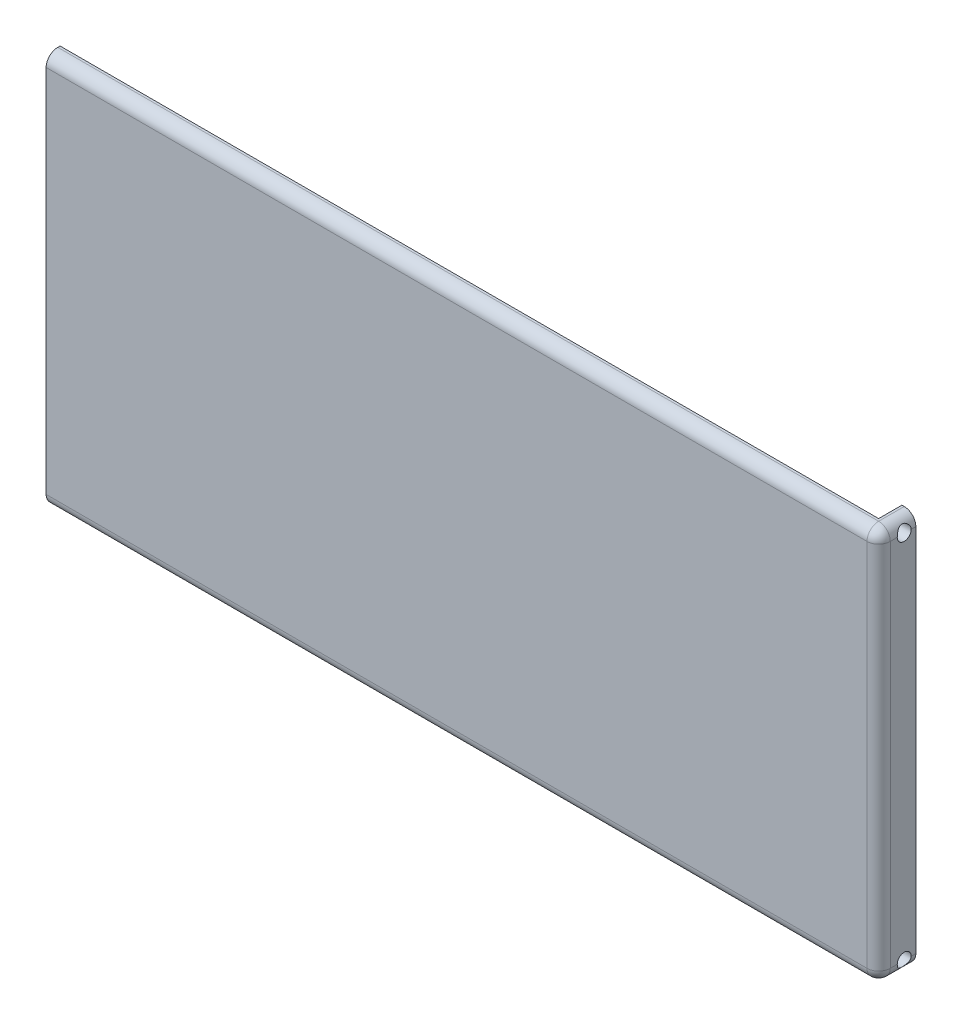
SolidWorks part; units mm, degrees
ref_plane "Front Plane" through (0, 0, 0) normal (0, 0, 1) x (1, 0, 0)
ref_plane "Top Plane" through (0, 0, 0) normal (0, 1, 0) x (1, 0, 0)
ref_plane "Right Plane" through (0, 0, 0) normal (1, 0, 0) x (0, 0, -1)
sketch "Sketch1" plane through (0, 0, 0) normal (0, 0, 1) x (1, 0, 0)
  line L1 (0, 0) -> (176, 0)
  line L2 (0, 0) -> (0, -84.5)
  line L3 (0, -84.5) -> (176, -84.5)
  line L4 (176, 0) -> (176, -84.5)
  point P4 (0, 0)
  dimension "D1" = 84.5
  dimension "D2" = 176
extrude "Boss-Extrude1" add sketch "Sketch1" along normal blind 3
sketch "Sketch2" plane through (176, 0, 0) normal (1, 0, 0) x (0, 0, -1)
  line L1 (-3, 0) -> (5, 0)
  line L2 (-3, 0) -> (-3, -5)
  line L3 (-3, -5) -> (5, -5)
  line L4 (5, 0) -> (5, -5)
  dimension "D1" = 5
  dimension "D2" = 8
extrude "Boss-Extrude2" add sketch "Sketch2" along normal blind 3
sketch "Sketch3" plane through (176, 0, 0) normal (-1, 0, 0) x (0, 0, 1)
  line L0 (0, -5) -> (0, -2.5) construction
  line L1 (0, -5) -> (0, 0) construction
  line L2 (0, -2.5) -> (-2.5, -2.5) construction
  line L3 (0, 0) -> (0, -84.5) construction
  circle A0 centre (-2.5, -2.5) radius 1.5
  dimension "D1" = 2.5
  dimension "D2" = 3
extrude "Cut-Extrude1" cut sketch "Sketch3" against normal blind 3
ref_plane "Plane4" through (0, -42.25, 0) normal (0, -1, 0) x (-1, 0, 0)
mirror "Mirror3" about plane through (0, -42.25, 0) normal (0, -1, 0) of "Cut-Extrude1", "Boss-Extrude2"
sketch "Sketch4" plane through (0, -79.5, 0) normal (0, 1, 0) x (1, 0, 0)
  line L1 (179, 5) -> (176, 5)
  line L2 (179, 5) -> (179, -3)
  line L3 (179, -3) -> (176, -3)
  line L4 (176, 5) -> (176, -3)
  point P5 (178.9287, 5)
  point P6 (0, 0)
extrude "Boss-Extrude3" add sketch "Sketch4" along normal up to surface (74.5 mm away) up to face at (177.2, -5, -0.8)
ref_plane "Plane5" through (89.5, 0, 0) normal (1, 0, 0) x (0, 0, -1)
ref_plane "Plane6" through (0, -70, 0) normal (0, -1, 0) x (-1, 0, 0)
ref_point "Point2"
sketch "Sketch12" plane through (0, -70, 0) normal (0, -1, 0) x (-1, 0, 0)
  line L0 (-176, -2.5) -> (-176, 0)
  line L1 (-176, 0) -> (-176, 5)
  line L2 (-176, 5) -> (-178.5, 5)
  line L3 (-178.5, 5) -> (-178.5, 0)
  arc A0 (-176, -2.5) -> (-178.5, 0) centre (-176, 0) cw
  dimension "D1" = 5
  dimension "D2" = 2.5
extrude "Cut-Extrude2" cut sketch "Sketch12" against normal blind 3.1
fillet "Fillet3" radius 2.5 1 edges at (179, -42.25, 3) type face fillet first side face at (179, -2.5, -1) second side face at (89.5, -42.25, 3)
fillet "Fillet4" radius 2.5 2 edges at (179, -84.5, -2.25) (88.25, -84.5, 3) type face fillet first side face at (126.7168, -84.5, -0.426) second side face at (88.25, -42.25, 3) second side face at (179, -2.5, -1)
fillet "Fillet7" radius 2.5 1 edges at (178.2678, 0, 2.2678) type face fillet first side face at (126.7168, 0, -0.426) second side face at (178.0089, -41, 2.0089)
pattern_linear "LPattern1" count 3 spacing 25 along (0, 1, 0) of "Cut-Extrude2"
